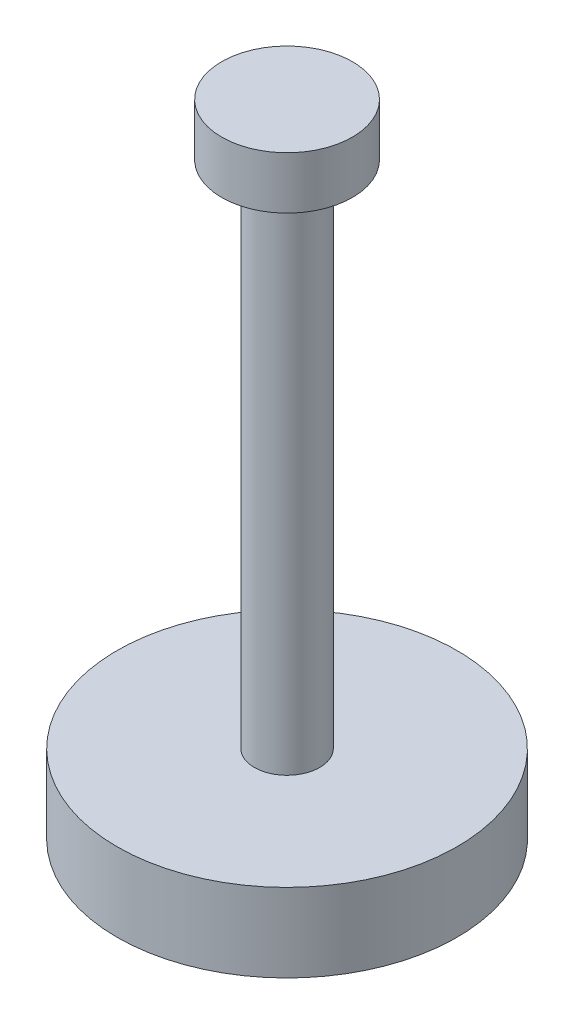
SolidWorks part; units mm, degrees
ref_plane "Front Plane" through (0, 0, 0) normal (0, 0, 1) x (1, 0, 0)
ref_plane "Top Plane" through (0, 0, 0) normal (0, 1, 0) x (1, 0, 0)
ref_plane "Right Plane" through (0, 0, 0) normal (1, 0, 0) x (0, 0, -1)
sketch "Sketch1" plane through (0, 0, 0) normal (0, 1, 0) x (1, 0, 0)
  circle A0 centre (0, 0) radius 6.35
  circle A1 centre (0, 0) radius 3.175
  circle A2 centre (0, 0) radius 16.51
  dimension "D1" = 33.02
  dimension "D2" = 12.7
  dimension "D3" = 6.35
extrude "Boss-Extrude1" add sketch "Sketch1" along normal blind 5.08 contours A0 A1 | A1 region at (-6.1704, 0, 0) region at (0, 0, 0)
extrude "Boss-Extrude2" add sketch "Sketch1<3>" against normal blind 49.53 contours A1 region at (0, 0, 0)
sketch "Sketch1<3>" plane through (0, 0, 0) normal (0, 1, 0) x (1, 0, 0) same geometry as "Sketch1"
extrude "Boss-Extrude3" add sketch "Sketch1<4>" against normal blind 7.62 from surface contours A1 | A0 A1 | A2 A0 region at (-6.1704, 0, 0) region at (0, 0, 0) region at (-16.043, 0, 0) starting at face at (0, -49.53, 3.175)
sketch "Sketch1<4>" plane through (0, 0, 0) normal (0, 1, 0) x (1, 0, 0) same geometry as "Sketch1"
